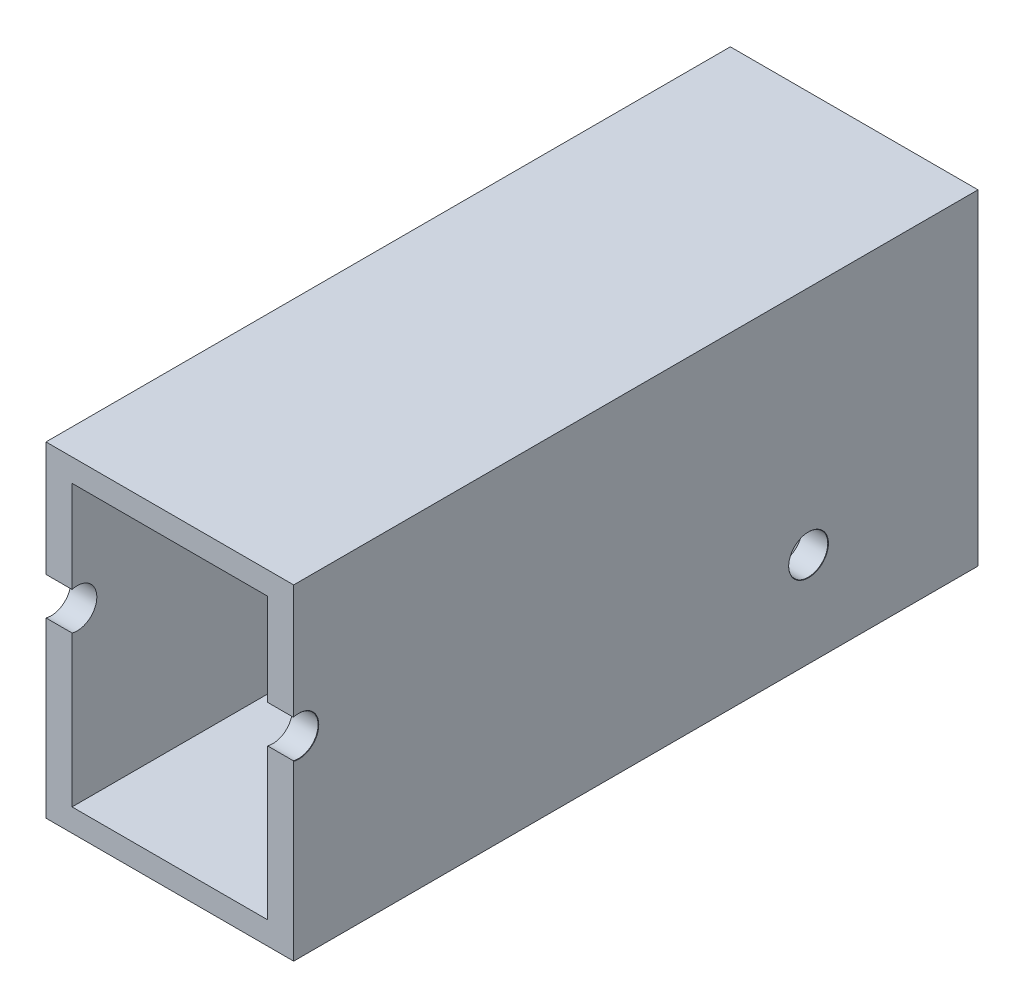
SolidWorks part; units mm, degrees
ref_plane "Front Plane" through (0, 0, 0) normal (1, 0, 0) x (0, 1, 0)
ref_plane "Top Plane" through (0, 0, 0) normal (0, 0, 1) x (0, 1, 0)
ref_plane "Right Plane" through (0, 0, 0) normal (0, 1, 0) x (-1, 0, 0)
sketch "Sketch1" plane through (0, 0, 0) normal (1, 0, 0) x (0, 1, 0)
  line L1 (-10.75, 21.25) -> (10.75, 21.25)
  line L2 (-10.75, 21.25) -> (-10.75, -21.25)
  line L3 (-10.75, -21.25) -> (10.75, -21.25)
  line L4 (10.75, 21.25) -> (10.75, -21.25)
  line L7 (10.75, -15.25) -> (-2.25, -15.25)
  line L8 (-2.25, -21.25) -> (-2.25, -15.25)
  line L9 (-12.5, 21.25) -> (12.5, 21.25)
  line L10 (-12.5, 21.25) -> (-12.5, -31.25)
  line L11 (-12.5, -31.25) -> (12.5, -31.25)
  line L12 (12.5, 21.25) -> (12.5, -31.25)
  point P4 (0, 21.25)
  point P6 (-10.75, 0)
  point P14 (0, 21.25)
  dimension "D1" = 0
  dimension "D2" = 0
  dimension "D3" = 42.5
  dimension "D4" = 21.5
  dimension "D5" = 36.5
  dimension "D6" = 13
  dimension "D7" = 0
  dimension "D8" = 10
  dimension "D9" = 25
  dimension "D10" = 0
extrude "Boss-Extrude1" add sketch "Sketch1" along normal blind 7.5 and the other way blind 7.5 contours L12 L9 L10 L11 L1 L4 L3 L2 | L8 L3 L4 L7 region at (0, -11.3315, 0) region at (0, 4.25, -18.25)
sketch "Sketch2" plane through (7.5, 0, 0) normal (1, 0, 0) x (0, 1, 0)
  line L1 (-12.5, 21.25) -> (12.5, 21.25)
  line L2 (-12.5, 21.25) -> (-12.5, -31.25)
  line L3 (-12.5, -31.25) -> (12.5, -31.25)
  line L4 (12.5, -31.25) -> (12.5, 21.25)
  line L5 (12.5, 21.25) -> (10.75, 21.25)
  line L6 (-12.5, 21.25) -> (-12.5, -31.25)
  line L7 (-12.5, -31.25) -> (12.5, -31.25)
  line L8 (12.5, -31.25) -> (12.5, 21.25)
  line L9 (12.5, 21.25) -> (10.75, 21.25)
  line L10 (-12.5, 21.25) -> (-12.5, -31.25)
  line L11 (-12.5, -31.25) -> (12.5, -31.25)
  line L12 (12.5, 21.25) -> (12.5, -31.25)
  line L22 (10.75, 21.25) -> (10.75, -15.25)
  line L23 (10.75, 21.25) -> (10.75, -15.25)
  line L24 (10.75, -15.25) -> (-2.25, -15.25)
  line L25 (10.75, -15.25) -> (-2.25, -15.25)
  line L26 (-2.25, -15.25) -> (-2.25, -21.25)
  line L27 (-2.25, -15.25) -> (-2.25, -21.25)
  line L28 (-2.25, -21.25) -> (-10.75, -21.25)
  line L29 (-2.25, -21.25) -> (-10.75, -21.25)
  line L30 (-10.75, -21.25) -> (-10.75, 21.25)
  line L31 (-10.75, -21.25) -> (-10.75, 21.25)
  line L32 (-10.75, 21.25) -> (-12.5, 21.25)
  line L33 (-10.75, 21.25) -> (-12.5, 21.25)
  line M5 (12.5, -31.25) -> (12.5, 21.25)
  line M6 (12.5, 21.25) -> (10.75, 21.25)
  line M7 (-12.5, 21.25) -> (-12.5, -31.25)
  line M8 (-12.5, -31.25) -> (12.5, -31.25)
  line M10 (10.75, 21.25) -> (10.75, -15.25)
  line M11 (10.75, -15.25) -> (-2.25, -15.25)
  line M12 (-2.25, -15.25) -> (-2.25, -21.25)
  line M13 (-2.25, -21.25) -> (-10.75, -21.25)
  line M14 (-10.75, -21.25) -> (-10.75, 21.25)
  dimension "D1" = 0
extrude "Boss-Extrude2" add sketch "Sketch2" along normal blind 2 contours M8 M5 M6 M7 M14 M10 M11 M12 M13 | M14 M13 M12 M11 M10 region at (7.5, 0.6953, -16.7509) region at (7.5, -0.3966, 1.7033)
sketch "Sketch5" plane through (9.5, 0, 0) normal (1, 0, 0) x (0, 1, 0)
  line L4 (-12.5, -31.25) -> (12.5, -31.25)
  line L5 (12.5, -31.25) -> (12.5, 21.25)
  line L6 (12.5, 21.25) -> (-12.5, 21.25)
  line L7 (-12.5, 21.25) -> (-12.5, -31.25)
  line L8 (-12.5, -31.25) -> (12.5, -31.25)
  line L9 (12.5, -31.25) -> (12.5, 21.25)
  line L10 (12.5, 21.25) -> (-12.5, 21.25)
  line L11 (-12.5, 21.25) -> (-12.5, -31.25)
  point P2 (-5.25, -18.25)
  point P61 (2.25, 20.85)
  dimension "D2" = 17.75
  dimension "D3" = 39.5
  dimension "D4" = 10.25
  dimension "D5" = 0.4
  dimension "D1" = 0
mirror "Mirror2" about plane through (0, 0, 0) normal (1, 0, 0) of "Boss-Extrude2"
hole_wizard "Ø3.0mm Dowel Hole1" positions "Sketch5" profile "Sketch6" hole size "Ø3.0" standard "IS" end condition through all
sketch "Sketch6" plane through (9.5, 2.25, 20.85) normal (0, 1, 0) x (0, 0, -1)
  line L0 (0, 0) -> (0, 19)
  line L1 (0, 19) -> (1.5, 19)
  line L2 (1.5, 19) -> (1.5, 0.025)
  line L3 (1.5, 0.025) -> (1.525, 0)
  line L5 (1.525, 0) -> (0, 0)
  line L6 (-1.5, 0.025) -> (-1.525, 0) construction
  line L11 (0, -6.35) -> (0, 107.95) construction
  dimension "Thru Hole Dia." = 3
  dimension "Thru Hole Depth" = 19
  dimension "Near C'Sink Dia." = 3.05
  dimension "Near C'Sink Angle" = 90
